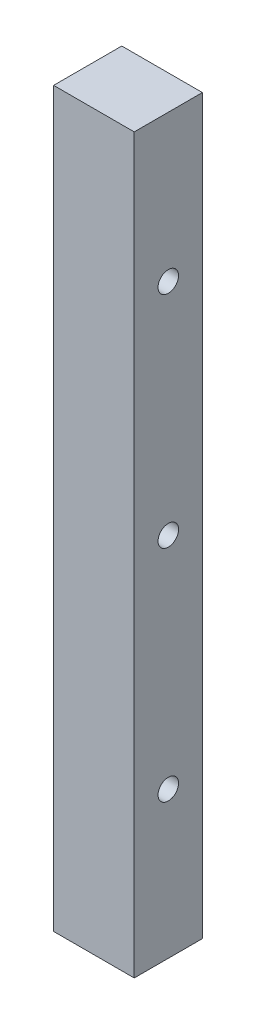
SolidWorks part; units mm, degrees
ref_plane "Front Plane" through (0, 0, 0) normal (0, 0, 1) x (1, 0, 0)
ref_plane "Top Plane" through (0, 0, 0) normal (0, 1, 0) x (1, 0, 0)
ref_plane "Right Plane" through (0, 0, 0) normal (1, 0, 0) x (0, 0, -1)
sketch "Sketch1" plane through (0, 0, 0) normal (0, 0, 1) x (1, 0, 0)
  line L1 (0, 0) -> (13.97, 0)
  line L2 (0, 0) -> (0, 127)
  line L3 (0, 127) -> (13.97, 127)
  line L4 (13.97, 0) -> (13.97, 127)
  dimension "D1" = 127
  dimension "D2" = 13.97
extrude "Boss-Extrude1" add sketch "Sketch1" along normal blind 11.811
sketch "Sketch2" plane through (0, 0, 0) normal (-1, 0, 0) x (0, 0, 1)
  line L0 (5.9055, 127) -> (5.9055, 0) construction
  line L1 (11.811, 127) -> (0, 127) construction
  line L2 (11.811, 0) -> (0, 0) construction
  circle A0 centre (5.9055, 101.6) radius 1.778
  circle A1 centre (5.9055, 63.5) radius 1.778
  circle A2 centre (5.9055, 25.4) radius 1.778
  point P24 (5.9055, 88.7418)
  dimension "D1" = 3.556
  dimension "D2" = 38.1
  dimension "D3" = 38.1
  dimension "D5" = 25.4
extrude "Cut-Extrude1" cut sketch "Sketch2" against normal through all
